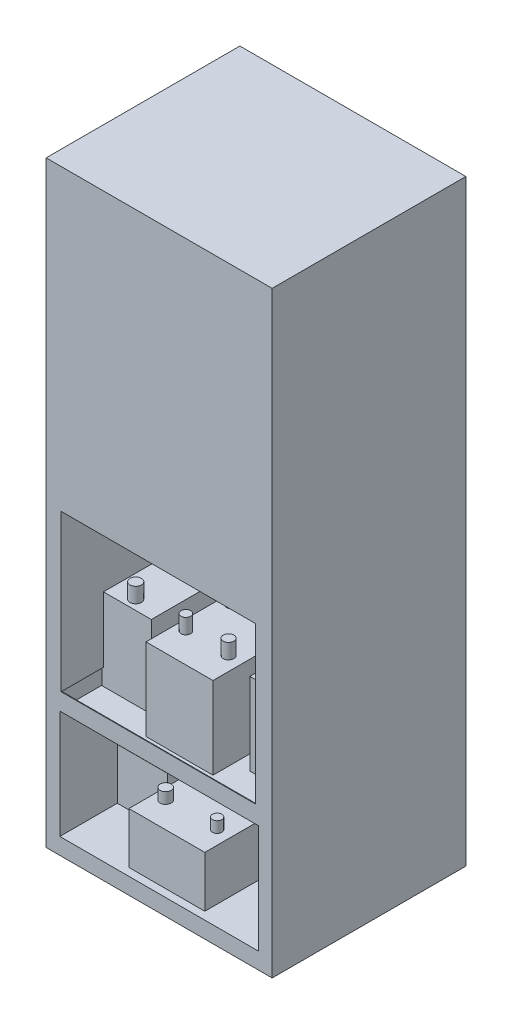
SolidWorks part; units mm, degrees
ref_plane "Alzado" through (0, 0, 0) normal (0, 0, 1) x (1, 0, 0)
ref_plane "Planta" through (0, 0, 0) normal (0, 1, 0) x (1, 0, 0)
ref_plane "Vista lateral" through (0, 0, 0) normal (1, 0, 0) x (0, 0, -1)
sketch "Croquis1" plane through (0, 0, 0) normal (0, 1, 0) x (1, 0, 0)
  line L1 (-350, 300) -> (350, 300)
  line L2 (-350, 300) -> (-350, -300)
  line L3 (-350, -300) -> (350, -300)
  line L4 (350, 300) -> (350, -300)
  line L5 (-350, 300) -> (350, -300) construction
  line L6 (-350, -300) -> (350, 300) construction
  point P0 (0, 0)
  dimension "D1" = 700
  dimension "D2" = 600
extrude "Saliente-Extruir1" add sketch "Croquis1" along normal blind 1850
sketch "Croquis2" plane through (0, 0, 300) normal (0, 0, 1) x (1, 0, 0)
  line L1 (-307.6068, 50.9) -> (307.6068, 50.9)
  line L2 (-307.6068, 50.9) -> (-307.6068, 387.2896)
  line L3 (-307.6068, 387.2896) -> (307.6068, 387.2896)
  line L4 (307.6068, 50.9) -> (307.6068, 387.2896)
  line L5 (-307.6068, 50.9) -> (307.6068, 387.2896) construction
  line L6 (-307.6068, 387.2896) -> (307.6068, 50.9) construction
  point P0 (0, 219.0948)
extrude "Cortar-Extruir1" cut sketch "Croquis2" against normal blind 1850
sketch "Croquis3" plane through (0, 0, 300) normal (0, 0, 1) x (1, 0, 0)
  line L1 (-303.7405, 925) -> (297.7312, 925)
  line L2 (-303.7405, 925) -> (-303.7405, 440.9417)
  line L3 (-303.7405, 440.9417) -> (297.7312, 440.9417)
  line L4 (297.7312, 925) -> (297.7312, 440.9417)
  line L5 (-303.7405, 925) -> (297.7312, 440.9417) construction
  line L6 (-303.7405, 440.9417) -> (297.7312, 925) construction
  point P0 (-3.0046, 682.9709)
extrude "Cortar-Extruir2" cut sketch "Croquis3" against normal blind 1850
shell "Vaciado1" thickness 2 removed face at (-3.0046, 440.9417, 0)
sketch "Croquis4" plane through (0, 389.2896, 0) normal (0, 1, 0) x (1, 0, 0)
  line L1 (149.6111, 168.6997) -> (305.4222, 168.6997)
  line L2 (149.6111, 168.6997) -> (149.6111, -168.6997)
  line L3 (149.6111, -168.6997) -> (305.4222, -168.6997)
  line L4 (305.4222, 168.6997) -> (305.4222, -168.6997)
  line L5 (149.6111, 168.6997) -> (305.4222, -168.6997) construction
  line L6 (149.6111, -168.6997) -> (305.4222, 168.6997) construction
  line L7 (-103.6465, 236.9965) -> (103.6465, 236.9965)
  line L8 (-103.6465, 236.9965) -> (-103.6465, -236.9965)
  line L9 (-103.6465, -236.9965) -> (103.6465, -236.9965)
  line L10 (103.6465, 236.9965) -> (103.6465, -236.9965)
  line L11 (-103.6465, 236.9965) -> (103.6465, -236.9965) construction
  line L12 (-103.6465, -236.9965) -> (103.6465, 236.9965) construction
  line L13 (-308.6569, 166.2136) -> (-155.4697, 166.2136)
  line L14 (-308.6569, 166.2136) -> (-308.6569, -168.6997)
  line L15 (-308.6569, -168.6997) -> (-155.4697, -168.6997)
  line L16 (-155.4697, 166.2136) -> (-155.4697, -168.6997)
  line L17 (-308.6569, 166.2136) -> (-155.4697, -168.6997) construction
  line L18 (-308.6569, -168.6997) -> (-155.4697, 166.2136) construction
  point P0 (227.5167, 0)
  point P5 (0, 0)
  point P11 (-232.0633, -1.2431)
extrude "Saliente-Extruir2" add sketch "Croquis4" along normal blind 254
sketch "Croquis5" plane through (0, 643.2896, 0) normal (0, 1, 0) x (1, 0, 0)
  circle A0 centre (230.0446, -120.7102) radius 17.6957
  circle A1 centre (230.0446, 47.3993) radius 17.6957
  circle A2 centre (-71.1508, -146.027) radius 14.8785
  circle A3 centre (-71.1508, 0) radius 20.0461
  circle A4 centre (-234.15, -138.406) radius 17.6957
  circle A5 centre (-234.15, 47.3993) radius 15.6127
  circle A6 centre (-71.1508, 166.6036) radius 20.0697
  circle A7 centre (61.0037, 0) radius 21.5153
  circle A8 centre (61.0037, 166.6036) radius 19.1168
  circle A9 centre (61.0037, -146.027) radius 16.4298
extrude "Saliente-Extruir3" add sketch "Croquis5" along normal blind 47
sketch "Croquis6" plane through (0, 50.9, 0) normal (0, 1, 0) x (1, 0, 0)
  line L1 (117.5503, -276.1799) -> (-117.5503, -276.1799)
  line L2 (117.5503, -276.1799) -> (117.5503, 276.1799)
  line L3 (117.5503, 276.1799) -> (-117.5503, 276.1799)
  line L4 (-117.5503, -276.1799) -> (-117.5503, 276.1799)
  line L5 (117.5503, -276.1799) -> (-117.5503, 276.1799) construction
  line L6 (117.5503, 276.1799) -> (-117.5503, -276.1799) construction
  line L7 (-152.4825, -121.9742) -> (-307.6068, -121.9742)
  line L8 (-152.4825, -121.9742) -> (-152.4825, 121.9742)
  line L9 (-152.4825, 121.9742) -> (-307.6068, 121.9742)
  line L10 (-307.6068, -121.9742) -> (-307.6068, 121.9742)
  line L11 (-152.4825, -121.9742) -> (-307.6068, 121.9742) construction
  line L12 (-152.4825, 121.9742) -> (-307.6068, -121.9742) construction
  line L13 (289.4517, -121.9742) -> (152.9417, -121.9742)
  line L14 (289.4517, -121.9742) -> (289.4517, 121.9742)
  line L15 (289.4517, 121.9742) -> (152.9417, 121.9742)
  line L16 (152.9417, -121.9742) -> (152.9417, 121.9742)
  line L17 (289.4517, -121.9742) -> (152.9417, 121.9742) construction
  line L18 (289.4517, 121.9742) -> (152.9417, -121.9742) construction
  point P0 (0, 0)
  point P6 (-230.0446, 0)
  point P11 (221.1967, 0)
extrude "Saliente-Extruir4" add sketch "Croquis6" along normal blind 158
sketch "Croquis7" plane through (0, 208.9, 0) normal (0, 1, 0) x (1, 0, 0)
  circle A0 centre (220.4901, -83.4417) radius 21.3099
  circle A1 centre (220.4901, 65.5487) radius 19.7092
  circle A2 centre (-83.7177, -196.0122) radius 17.1385
  circle A3 centre (75.6701, -196.0122) radius 14.5387
  circle A4 centre (-83.7177, 0) radius 19.1962
  circle A5 centre (75.6701, 5.9526) radius 15.4246
  circle A6 centre (-83.7177, 184.741) radius 17.9954
  circle A7 centre (75.6701, 184.741) radius 20.52
  circle A8 centre (-230.0446, -62.1317) radius 17.445
  circle A9 centre (-230.0446, 45.8395) radius 21.1159
extrude "Saliente-Extruir5" add sketch "Croquis7" along normal blind 34
sketch "Croquis8" plane through (0, 0, -300) normal (0, 0, -1) x (-1, 0, 0)
  line L1 (-250.0903, 1244.3934) -> (250.0903, 1244.3934)
  line L2 (-300.0903, 1294.3934) -> (-300.0903, 1716.6284)
  line L3 (-250.0903, 1766.6284) -> (250.0903, 1766.6284)
  line L4 (300.0903, 1294.3934) -> (300.0903, 1716.6284)
  line L5 (-300.0903, 1244.3934) -> (300.0903, 1766.6284) construction
  line L6 (-300.0903, 1766.6284) -> (300.0903, 1244.3934) construction
  arc A0 (-250.0903, 1244.3934) -> (-300.0903, 1294.3934) centre (-250.0903, 1294.3934) cw
  arc A1 (250.0903, 1244.3934) -> (300.0903, 1294.3934) centre (250.0903, 1294.3934) ccw
  arc A2 (250.0903, 1766.6284) -> (300.0903, 1716.6284) centre (250.0903, 1716.6284) cw
  arc A3 (-300.0903, 1716.6284) -> (-250.0903, 1766.6284) centre (-250.0903, 1716.6284) cw
  point P0 (0, 1505.5109)
  dimension "D1" = 50
extrude "Saliente-Extruir6" add sketch "Croquis8" along normal blind 34
sketch "Croquis9" plane through (0, 0, -334) normal (0, 0, -1) x (-1, 0, 0)
  line L1 (-270.6006, 1733.8635) -> (-189.3334, 1733.8635)
  line L2 (-278.6006, 1725.8635) -> (-278.6006, 1662.2812)
  line L3 (-270.6006, 1654.2812) -> (-189.3334, 1654.2812)
  line L4 (-181.3334, 1725.8635) -> (-181.3334, 1662.2812)
  line L5 (-278.6006, 1733.8635) -> (-181.3334, 1654.2812) construction
  line L6 (-278.6006, 1654.2812) -> (-181.3334, 1733.8635) construction
  line L7 (-51.3176, 1706.4822) -> (264.6067, 1706.4822)
  line L8 (-64.3176, 1693.4822) -> (-64.3176, 1530.5631)
  line L9 (-51.3176, 1517.5631) -> (264.6067, 1517.5631)
  line L10 (277.6067, 1693.4822) -> (277.6067, 1530.5631)
  line L11 (-64.3176, 1706.4822) -> (277.6067, 1517.5631) construction
  line L12 (-64.3176, 1517.5631) -> (277.6067, 1706.4822) construction
  arc A0 (-64.3176, 1530.5631) -> (-51.3176, 1517.5631) centre (-51.3176, 1530.5631) ccw
  arc A1 (264.6067, 1517.5631) -> (277.6067, 1530.5631) centre (264.6067, 1530.5631) ccw
  arc A2 (264.6067, 1706.4822) -> (277.6067, 1693.4822) centre (264.6067, 1693.4822) cw
  arc A3 (-51.3176, 1706.4822) -> (-64.3176, 1693.4822) centre (-51.3176, 1693.4822) ccw
  arc A4 (-278.6006, 1662.2812) -> (-270.6006, 1654.2812) centre (-270.6006, 1662.2812) ccw
  arc A5 (-189.3334, 1654.2812) -> (-181.3334, 1662.2812) centre (-189.3334, 1662.2812) ccw
  arc A6 (-270.6006, 1733.8635) -> (-278.6006, 1725.8635) centre (-270.6006, 1725.8635) ccw
  arc A7 (-189.3334, 1733.8635) -> (-181.3334, 1725.8635) centre (-189.3334, 1725.8635) cw
  point P0 (-229.967, 1694.0724)
  point P5 (106.6446, 1612.0227)
  dimension "D1" = 13
  dimension "D2" = 8
extrude "Cortar-Extruir3" cut sketch "Croquis9" against normal blind 0.2
sketch "Croquis10" plane through (0, 0, -334) normal (0, 0, -1) x (-1, 0, 0)
  line L0 (-266.9064, 1336.5619) -> (-8.2826, 1336.5619) construction
  text T0 "SEDPC" font "Century Gothic" height in points 250
extrude "Cortar-Extruir4" cut sketch "Croquis10" against normal blind 0.2
sketch "Croquis11" plane through (0, 0, -300) normal (0, 0, -1) x (-1, 0, 0)
  circle A0 centre (-331.1303, 1826.0494) radius 8.6382
  circle A1 centre (331.4196, 1826.0494) radius 9.502
extrude "Cortar-Extruir5" cut sketch "Croquis11" against normal blind 0.2
pattern_linear "MatrizL1" count 36 spacing 50 along (0, -1, 0) of "Cortar-Extruir5"
sketch "Croquis12" plane through (0, 0, -300) normal (0, 0, -1) x (-1, 0, 0)
  circle A0 centre (-277.5665, 414.7202) radius 7.9
extrude "Cortar-Extruir6" cut sketch "Croquis12" against normal blind 0.2
pattern_linear "MatrizL2" count 30 spacing 20 along (-1, 0, 0) of "Cortar-Extruir6"
